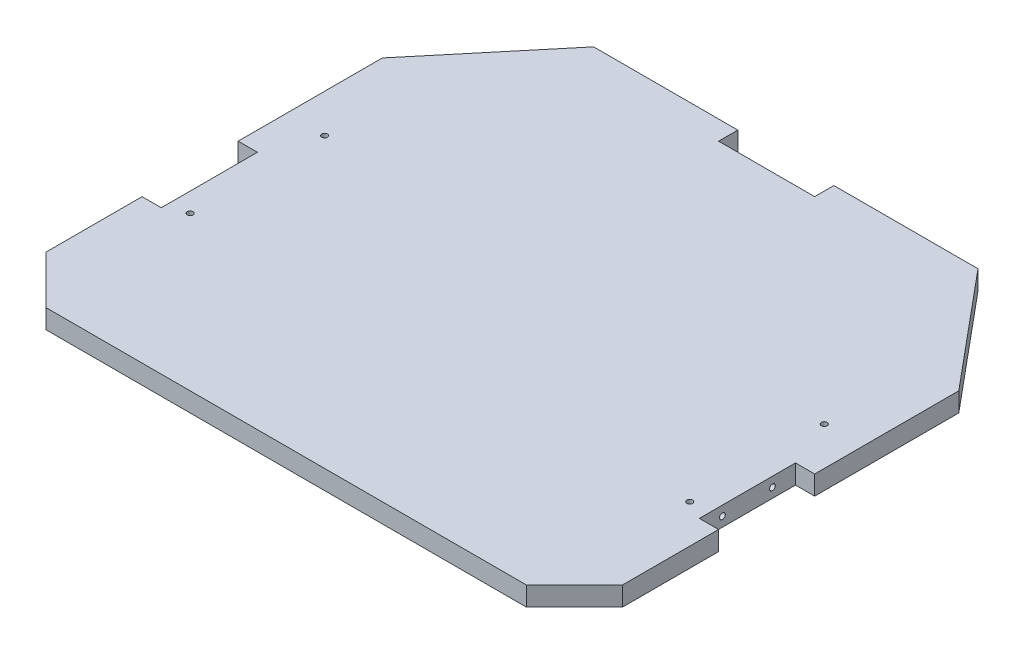
SolidWorks part; units mm, degrees
material "ABS PC"
ref_plane "Спереди" through (0, 0, 0) normal (0, 0, 1) x (1, 0, 0)
ref_plane "Сверху" through (0, 0, 0) normal (0, 1, 0) x (1, 0, 0)
ref_plane "Справа" through (0, 0, 0) normal (1, 0, 0) x (0, 0, -1)
sketch "Sketch1" plane through (0, 0, 0) normal (0, 1, 0) x (1, 0, 0)
  line L0 (-150, 200) -> (-150, 125)
  line L1 (-150, 200) -> (-100, 260)
  line L2 (-100, 260) -> (-25, 260)
  line L3 (0, 260) -> (0, 0) construction
  line L4 (-25, 260) -> (-25, 250)
  line L6 (-25, 250) -> (25, 250)
  line L7 (-150, 125) -> (-140, 125)
  line L8 (-140, 125) -> (-140, 75)
  line L9 (-140, 75) -> (-150, 75)
  line L10 (-150, 75) -> (-150, 25)
  line L11 (-25, 260) -> (25, 260) construction
  line L12 (-150, 125) -> (-150, 75) construction
  line L13 (150, 260) -> (100, 260) construction
  line L14 (150, 200) -> (150, 260) construction
  line L15 (150, 125) -> (150, 75) construction
  line L16 (-125, 0) -> (125, 0)
  line L17 (150, 0) -> (125, 0) construction
  line L18 (-150, 200) -> (-150, 260) construction
  line L19 (-150, 260) -> (-100, 260) construction
  line L20 (140, 75) -> (150, 75)
  line L21 (140, 125) -> (140, 75)
  line L22 (150, 125) -> (140, 125)
  line L23 (150, 25) -> (150, 0) construction
  line L24 (25, 260) -> (25, 250)
  line L25 (100, 260) -> (25, 260)
  line L26 (150, 200) -> (100, 260)
  line L27 (150, 200) -> (150, 125)
  line L28 (-150, 25) -> (-125, 0)
  line L29 (-150, 25) -> (-150, 0) construction
  line L30 (-150, 0) -> (-125, 0) construction
  line L31 (150, 25) -> (125, 0)
  line L32 (150, 75) -> (150, 25)
  point P25 (0, 250)
  dimension "D2" = 150
  dimension "D3" = 60
  dimension "D4" = 50
  dimension "D5" = 50
  dimension "D6" = 25
  dimension "D7" = 75
  dimension "D8" = 10
  dimension "D9" = 25
  dimension "D10" = 25
  dimension "D11" = 260
extrude "Boss-Extrude1" add sketch "Sketch1" along normal blind 10 contours L3 L1 L26 L7 | L3 region at (0, 0, -126.0692)
sketch "Sketch2" plane through (-140, 0, 0) normal (-1, 0, 0) x (0, 0, 1)
  line L0 (-125, 10) -> (-125, 0) construction
  line L1 (-75, 10) -> (-75, 0) construction
  line L2 (-125, 10) -> (-75, 10) construction
  circle A0 centre (-113, 5) radius 1.5
  circle A1 centre (-87, 5) radius 1.5
  point P6 (-75, 5)
  dimension "D1" = 3
  dimension "D2" = 12
  dimension "D3" = 12
  dimension "D4" = 5
extrude "Cut-Extrude1" cut sketch "Sketch2" against normal blind 15
mirror "Mirror1" about plane through (0, 0, 0) normal (1, 0, 0) of "Cut-Extrude1"
sketch "Sketch3" plane through (0, 0, -250) normal (0, 0, -1) x (-1, 0, 0)
  line L0 (-25, 10) -> (-25, 0) construction
  line L1 (25, 10) -> (25, 0) construction
  line L2 (25, 10) -> (-25, 10) construction
  circle A0 centre (-13, 5) radius 1.5
  circle A1 centre (13, 5) radius 1.5
  dimension "D1" = 3
  dimension "D2" = 12
  dimension "D3" = 12
  dimension "D4" = 5
extrude "Cut-Extrude2" cut sketch "Sketch3" against normal blind 15
sketch "Sketch4" plane through (0, 10, 0) normal (0, 1, 0) x (1, 0, 0)
  line L0 (-140, 125) -> (-140, 75) construction
  line L1 (-150, 125) -> (-140, 125) construction
  circle A0 centre (-130, 80) radius 1.5
  circle A1 centre (-130, 150) radius 1.5
  dimension "D1" = 3
  dimension "D2" = 10
  dimension "D4" = 70
  dimension "D3" = 25
extrude "Cut-Extrude3" cut sketch "Sketch4" against normal up to next
mirror "Mirror2" about plane through (0, 0, 0) normal (1, 0, 0) of "Cut-Extrude3"
